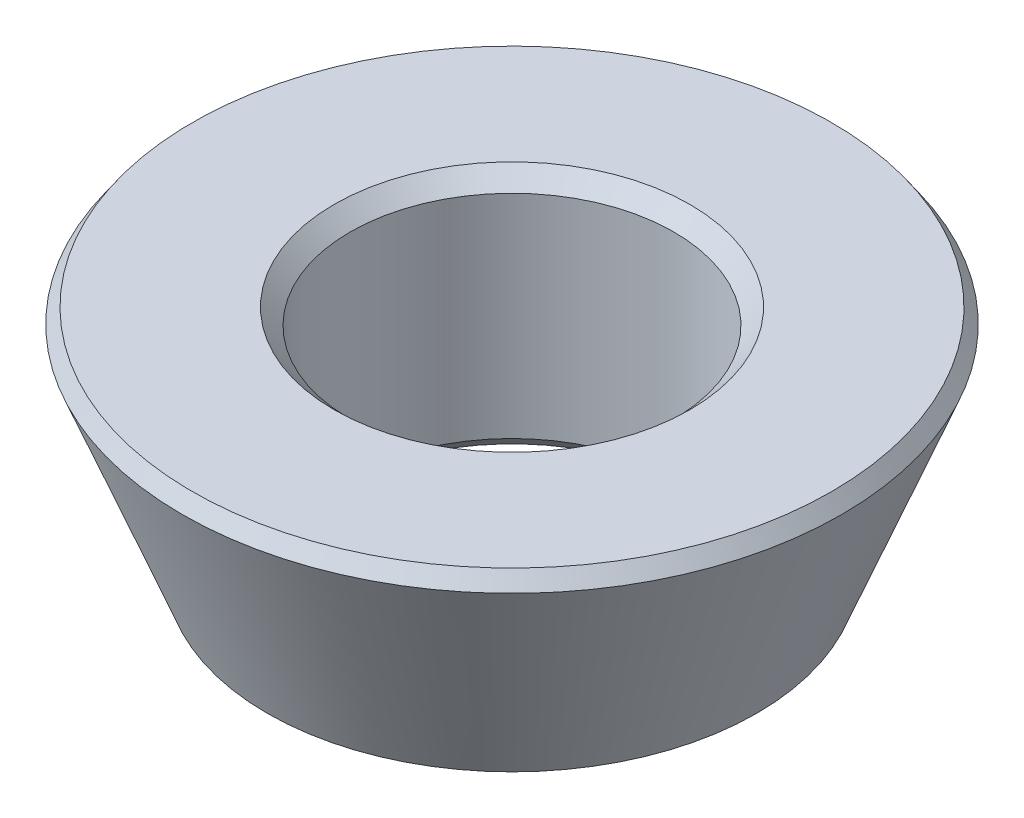
SolidWorks part; units mm, degrees
ref_plane "Front Plane" through (0, 0, 0) normal (0, 0, 1) x (1, 0, 0)
ref_plane "Top Plane" through (0, 0, 0) normal (0, 1, 0) x (1, 0, 0)
ref_plane "Right Plane" through (0, 0, 0) normal (1, 0, 0) x (0, 0, -1)
sketch "Sketch3" plane through (0, 0, 0) normal (0, 0, 1) x (1, 0, 0)
  line L0 (0, 0) -> (4.5, 0)
  line L1 (4.5, 0) -> (6.3198, 4.6)
  line L2 (6.3198, 4.6) -> (0, 4.6)
  line L3 (0, 4.6) -> (0, 0)
  line L4 (3.05, 4.6) -> (3.05, 0)
  point P7 (6.3198, 4.6)
  point P8 (4.6257, 0)
  dimension "D1" = 4.6
  dimension "D2" = 6.3198
  dimension "D3" = 3.05
  dimension "D4" = 4.5
revolve "Revolve1" add sketch "Sketch3" angle 360 about L3 region at (4.2884, 2.5956, 0)
chamfer "Chamfer3" distance 0.3 distance2 0.3 4 edges at (-3.05, 4.6, 0) (-3.05, 0, 0) (-4.5, 0, 0) (-6.3198, 4.6, 0)
